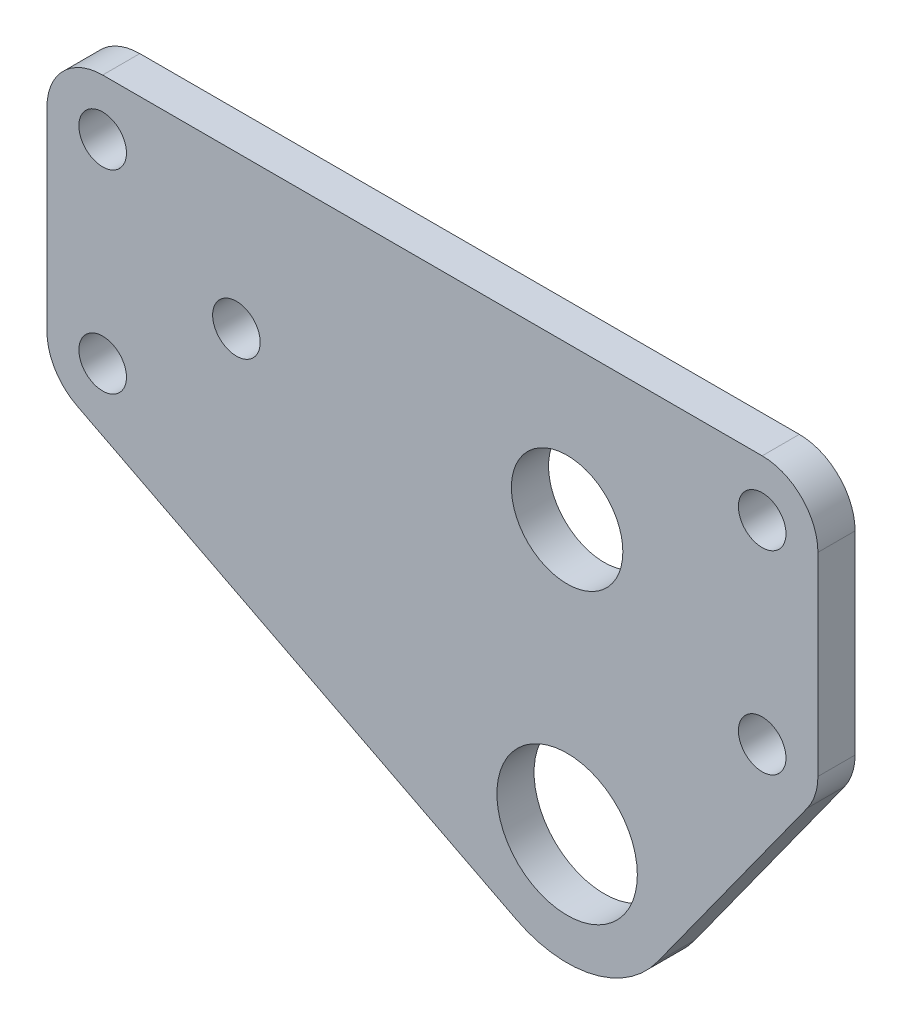
SolidWorks part; units mm, degrees
ref_plane "Front Plane" through (0, 0, 0) normal (0, 0, 1) x (1, 0, 0)
ref_plane "Top Plane" through (0, 0, 0) normal (0, 1, 0) x (1, 0, 0)
ref_plane "Right Plane" through (0, 0, 0) normal (1, 0, 0) x (0, 0, -1)
sketch "Sketch1" plane through (0, 0, 0) normal (0, 0, 1) x (1, 0, 0)
  line L0 (0, 0) -> (26.9875, 0) construction
  line L2 (43.6562, -13.0556) -> (-16.6687, -13.0556)
  line L3 (48.4188, -8.2931) -> (48.4188, 8.2931)
  line L4 (43.6562, 13.0556) -> (-16.6687, 13.0556)
  line L5 (-21.4312, -8.2931) -> (-21.4312, 8.2931)
  line L6 (48.4188, -13.0556) -> (-21.4312, 13.0556) construction
  line L7 (48.4188, 13.0556) -> (-21.4312, -13.0556) construction
  circle A0 centre (0, 0) radius 6 construction
  circle A1 centre (26.9875, 0) radius 4.7625
  arc A2 (48.4188, 8.2931) -> (43.6562, 13.0556) centre (43.6562, 8.2931) ccw
  arc A3 (43.6562, -13.0556) -> (48.4188, -8.2931) centre (43.6562, -8.2931) ccw
  arc A4 (-16.6687, -13.0556) -> (-21.4312, -8.2931) centre (-16.6687, -8.2931) cw
  arc A5 (-16.6687, 13.0556) -> (-21.4312, 8.2931) centre (-16.6687, 8.2931) ccw
  circle A6 centre (0, 0) radius 13.7592 construction
  circle A7 centre (26.9875, 0) radius 15.3467 construction
  circle A8 centre (-16.6687, 8.2931) radius 2.032 construction
  circle A9 centre (43.6562, 8.2931) radius 2.032
  circle A10 centre (-16.6687, -8.2931) radius 2.032 construction
  circle A11 centre (43.6562, -8.2931) radius 2.032
  circle A12 centre (-1.27, 0) radius 2.032
  point P5 (13.4937, 0)
  dimension "D1" = 12
  dimension "D2" = 26.9875
  dimension "D5" = 4.7625
  dimension "D6" = 27.5184
  dimension "D7" = 30.6934
  dimension "D8" = 4.064
  dimension "D9" = 9.525
  dimension "D3" = 26.1112
  dimension "D4" = 15.3987
  dimension "D10" = 28.2575
extrude "Boss-Extrude1" add sketch "Sketch1" along normal blind 3.175
sketch "Sketch4" plane through (0, 0, 3.175) normal (0, 0, 1) x (1, 0, 0)
  line L0 (-17.4625, 8.2931) -> (-17.4625, -8.2931)
  line L1 (43.6562, 13.0556) -> (-16.6687, 13.0556) construction
  line L2 (-16.6687, -13.0556) -> (43.6562, -13.0556) construction
  line L3 (-16.6687, -13.0556) -> (-12.7, -13.0556)
  line L4 (43.6562, 13.0556) -> (-16.6687, 13.0556)
  line L5 (-21.4312, 8.2931) -> (-21.4312, -8.2931)
  line L6 (-16.6687, -13.0556) -> (43.6562, -13.0556)
  line L7 (48.4188, -8.2931) -> (48.4188, 8.2931)
  line L8 (-12.7, 13.0556) -> (-16.6687, 13.0556)
  line L9 (-21.4312, 8.2931) -> (-21.4312, -8.2931)
  arc A0 (-17.4625, 8.2931) -> (-12.7, 13.0556) centre (-12.7, 8.2931) cw
  arc A1 (-17.4625, -8.2931) -> (-12.7, -13.0556) centre (-12.7, -8.2931) ccw
  circle A2 centre (-12.7, -8.2931) radius 2.032
  circle A3 centre (-12.7, 8.2931) radius 2.032
  arc A4 (48.4188, 8.2931) -> (43.6562, 13.0556) centre (43.6562, 8.2931) ccw
  arc A5 (-16.6687, 13.0556) -> (-21.4312, 8.2931) centre (-16.6687, 8.2931) ccw
  arc A6 (-21.4312, -8.2931) -> (-16.6687, -13.0556) centre (-16.6687, -8.2931) ccw
  arc A7 (43.6562, -13.0556) -> (48.4188, -8.2931) centre (43.6562, -8.2931) ccw
  arc A9 (-16.6687, 13.0556) -> (-21.4312, 8.2931) centre (-16.6687, 8.2931) ccw
  arc A10 (-21.4312, -8.2931) -> (-16.6687, -13.0556) centre (-16.6687, -8.2931) ccw
  dimension "D3" = 4.064
  dimension "D2" = 3.9688
  dimension "D1" = 0
extrude "Cut-Extrude1" cut sketch "Sketch4" against normal through all
sketch "Sketch2" plane through (0, 0, 3.175) normal (0, 0, 1) x (1, 0, 0)
  line L0 (26.9875, 0) -> (26.9875, -23.2833) construction
  line L1 (22.6429, -31.7598) -> (-14.8723, -12.5313)
  line L2 (34.7159, -28.8509) -> (47.5204, -11.0769)
  line L3 (-12.7, -13.0556) -> (43.6562, -13.0556) construction
  line L4 (-12.7, -13.0556) -> (43.6562, -13.0556)
  circle A0 centre (26.9875, -23.2833) radius 6
  arc A1 (22.6429, -31.7598) -> (34.7159, -28.8509) centre (26.9875, -23.2833) ccw
  arc A3 (-17.4625, -8.2931) -> (-12.7, -13.0556) centre (-12.7, -8.2931) ccw construction
  arc A4 (43.6562, -13.0556) -> (48.4188, -8.2931) centre (43.6562, -8.2931) ccw construction
  arc A5 (-14.8723, -12.5313) -> (-12.7, -13.0556) centre (-12.7, -8.2931) ccw
  arc A6 (43.6562, -13.0556) -> (47.5204, -11.0769) centre (43.6562, -8.2931) ccw
  point P6 (-14.9791, -12.4748)
  dimension "D1" = 12
  dimension "D3" = 9.525
  dimension "D2" = 23.2833
extrude "Boss-Extrude2" add sketch "Sketch2" against normal up to surface (3.175 mm away) up to face at (-10.668, 8.2931, 0)
